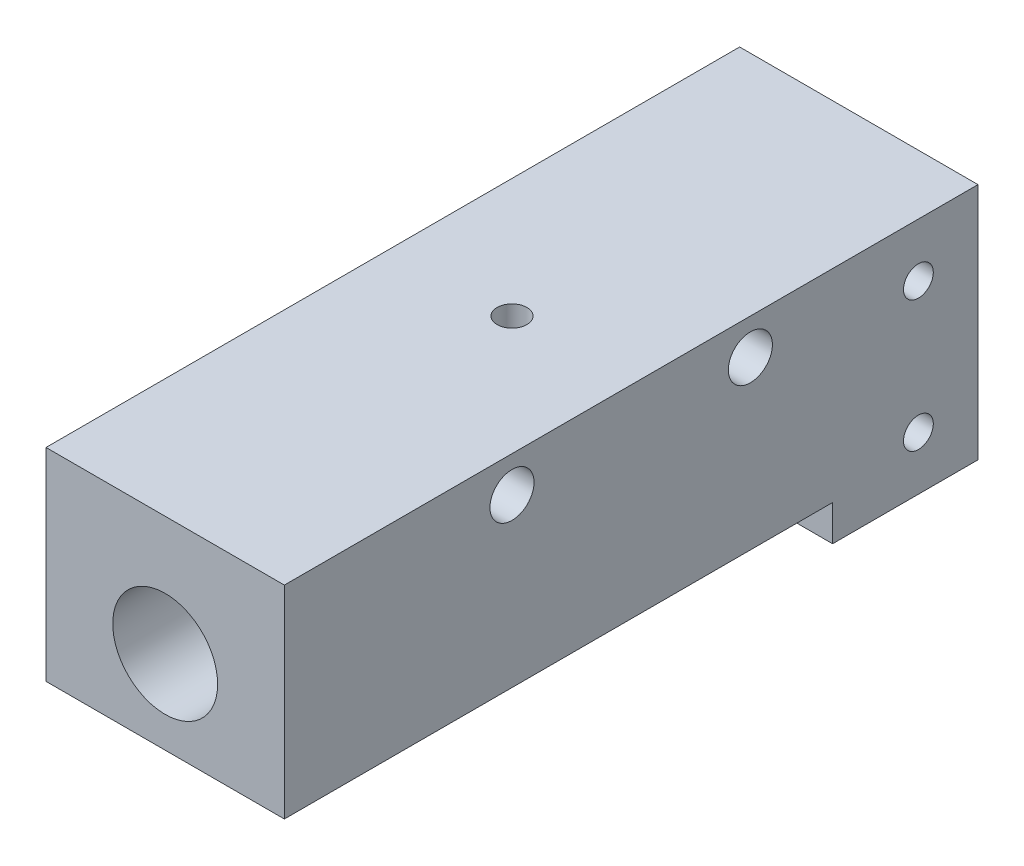
SolidWorks part; units mm, degrees
material "6063-T5"
ref_plane "Piano frontale" through (0, 0, 0) normal (0, 0, 1) x (1, 0, 0)
ref_plane "Piano superiore" through (0, 0, 0) normal (0, 1, 0) x (1, 0, 0)
ref_plane "Piano destro" through (0, 0, 0) normal (1, 0, 0) x (0, 0, -1)
sketch "Schizzo1" plane through (0, 0, 0) normal (0, 0, 1) x (1, 0, 0)
  line L1 (10, -10) -> (-10, -10)
  line L2 (10, -10) -> (10, 10)
  line L3 (10, 10) -> (-10, 10)
  line L4 (-10, -10) -> (-10, 10)
  line L5 (10, -10) -> (-10, 10) construction
  line L6 (10, 10) -> (-10, -10) construction
  point P0 (0, 0)
  dimension "D1" = 20
  dimension "D2" = 20
extrude "Estrusione-Estrusione1" add sketch "Schizzo1" against normal blind 58.2
sketch "Schizzo2" plane through (0, 0, -58.2) normal (0, 0, -1) x (-1, 0, 0)
  circle A0 centre (0, 0) radius 3
  dimension "D1" = 6
extrude "Taglio-Estrusione1" cut sketch "Schizzo2" against normal through all
sketch "Schizzo3" plane through (0, 0, -58.2) normal (0, 0, -1) x (-1, 0, 0)
  point P0 (0, 0)
sketch "Schizzo4" plane through (10, 0, 0) normal (1, 0, 0) x (0, 0, -1)
  line L0 (0, 7) -> (58.2, 7) construction
  line L1 (0, -10) -> (0, 10) construction
  line L2 (58.2, -10) -> (58.2, 10) construction
  line L3 (58.2, 10) -> (0, 10) construction
  line L4 (29.1, 10) -> (29.1, -10) construction
  line L5 (58.2, -10) -> (0, -10) construction
  circle A0 centre (19.1, 7) radius 1.85
  circle A1 centre (39.1, 7) radius 1.85
  dimension "D2" = 3.7
  dimension "D1" = 3
  dimension "D3" = 10
  dimension "D4" = 19.1
extrude "Taglio-Estrusione3" cut sketch "Schizzo4" against normal through all
hole_wizard "Foro filettato G1/8-1" positions "Schizzo8" profile "Schizzo7" tap size "G1/8" standard "BSI"
sketch "Schizzo8" plane through (0, 0, 0) normal (0, 0, 1) x (1, 0, 0)
  point P0 (0, 0)
sketch "Schizzo7" plane through (0, 0, 0) normal (1, 0, 0) x (0, -1, 0)
  line L0 (0, 0) -> (0, 12.6438)
  line L1 (0, 12.6438) -> (4.4, 10)
  line L2 (4.4, 10) -> (4.4, 0)
  line L5 (4.4, 0) -> (0, 0)
  line L10 (0, 12.6438) -> (-4.4, 10) construction
  line L11 (0, -6.35) -> (0, 107.95) construction
  dimension "Tap Drill Dia." = 8.8
  dimension "Tap Drill Depth" = 10
  dimension "Drill Angle" = 118
sketch "Schizzo10" plane through (10, 0, 0) normal (1, 0, 0) x (0, 0, -1)
  line L0 (0, -7) -> (46, -7)
  line L1 (0, -10) -> (0, 10) construction
  line L2 (46, -7) -> (46, -10)
  line L3 (58.2, -10) -> (0, -10) construction
  dimension "D1" = 46
  dimension "D2" = 3
extrude "Taglio-Estrusione5" cut sketch "Schizzo10" against normal through all and the other way through all flip side to cut
sketch "Schizzo11" plane through (0, 10, 0) normal (0, 1, 0) x (1, 0, 0)
  line L0 (0, 58.2) -> (0, 0) construction
  line L1 (10, 58.2) -> (-10, 58.2) construction
  line L2 (10, 29.1) -> (-10, 29.1) construction
  line L3 (10, 58.2) -> (10, 0) construction
  point P10 (0, 29.1)
  point P11 (0, 29.1)
  point P12 (0, 29.1)
hole_wizard "Foro filettato M3-1" positions "Schizzo3D1" profile "Schizzo12" tap size "M3" standard "DIN"
sketch3d "Schizzo3D1"
  point P0 (0, 10, -29.1)
sketch "Schizzo12" plane through (0, 10, -29.1) normal (1, 0, 0) x (0, 0, 1)
  line L0 (0, 0) -> (0, 5.7511)
  line L1 (0, 5.7511) -> (1.25, 5)
  line L2 (1.25, 5) -> (1.25, 0)
  line L5 (1.25, 0) -> (0, 0)
  line L10 (0, 5.7511) -> (-1.25, 5) construction
  line L11 (0, -6.35) -> (0, 107.95) construction
  dimension "Tap Drill Dia." = 2.5
  dimension "Tap Drill Depth" = 5
  dimension "Drill Angle" = 118
hole_wizard "Foro Ø16.0 (16)-1" positions "Schizzo3D3" profile "Schizzo14" hole size "Ø16.0" standard "ISO"
sketch3d "Schizzo3D3"
  point P0 (0, 0, 0)
  point P3 (0, 0, -58.2)
sketch "Schizzo14" plane through (0, 0, -58.2) normal (1, 0, 0) x (0, 1, 0)
  line L0 (0, 0) -> (0, 16.8069)
  line L1 (0, 16.8069) -> (8, 12)
  line L2 (8, 12) -> (8, 0)
  line L5 (8, 0) -> (0, 0)
  line L10 (0, 16.8069) -> (-8, 12) construction
  line L11 (0, -6.35) -> (0, 107.95) construction
  dimension "Hole Dia." = 16
  dimension "Hole Depth" = 12
  dimension "Drill Angle" = 118
sketch "Schizzo15" plane through (10, 0, 0) normal (1, 0, 0) x (0, 0, -1)
  line L0 (46.2, 0) -> (58.2, 0) construction
  line L1 (46.2, 8) -> (46.2, -8) construction
  line L4 (58.2, -10) -> (58.2, 10) construction
  line L6 (58.2, -10) -> (46, -10) construction
  point P5 (53.2, -5.5)
  point P8 (53.2, 5.5)
  dimension "D1" = 5.5
  dimension "D2" = 7
  dimension "D3" = 5
  dimension "D4" = 4.5
hole_wizard "Foro filettato M3-2" positions "Schizzo3D4" profile "Schizzo16" tap size "M3" standard "ISO" end condition through all
sketch3d "Schizzo3D4"
  point P0 (10, 5.5, -53.2)
  point P3 (10, -5.5, -53.2)
sketch "Schizzo16" plane through (10, 5.5, -53.2) normal (0, 1, 0) x (0, 0, -1)
  line L0 (0, 0) -> (0, 20)
  line L1 (0, 20) -> (1.25, 20)
  line L2 (1.25, 20) -> (1.25, 0)
  line L5 (1.25, 0) -> (0, 0)
  line L11 (0, -6.35) -> (0, 107.95) construction
  dimension "Thread Major Dia." = 2.5
  dimension "Thru Tap Drill Depth" = 20
